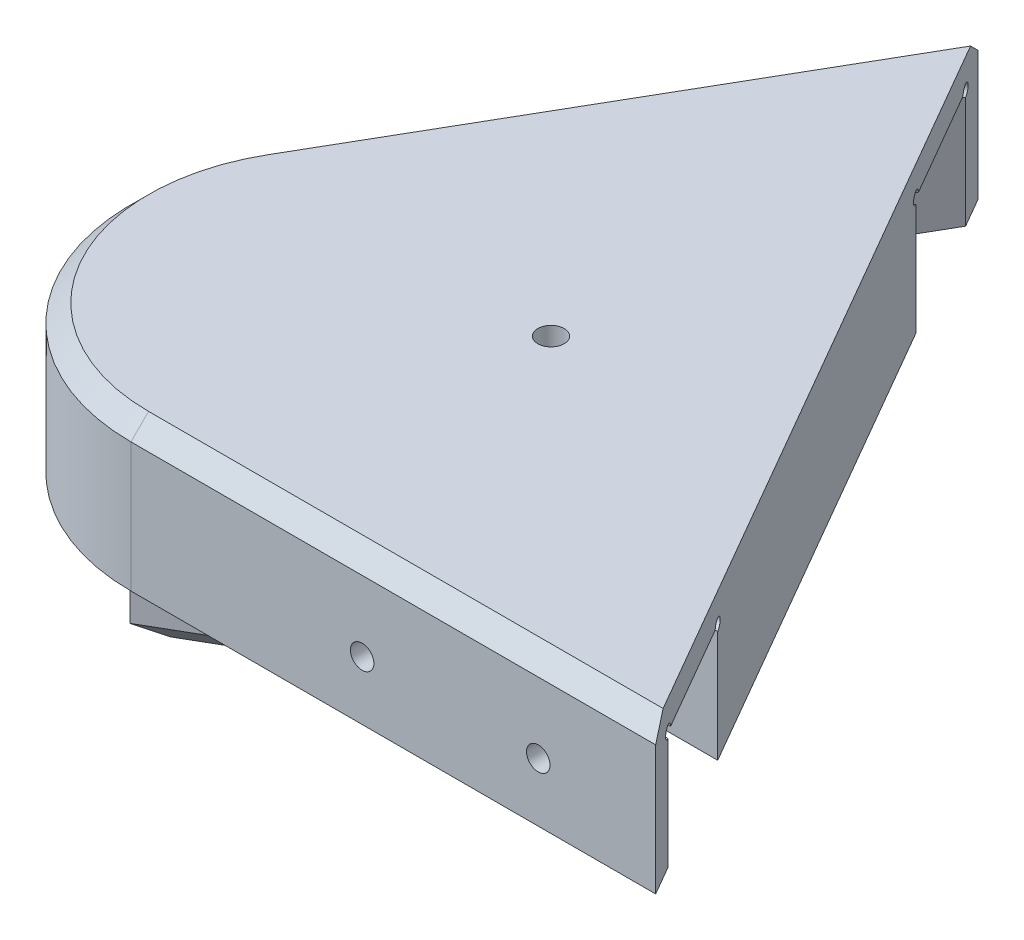
SolidWorks part; units mm, degrees
ref_plane "Front Plane" through (0, 0, 0) normal (0, 0, 1) x (1, 0, 0)
ref_plane "Top Plane" through (0, 0, 0) normal (0, 1, 0) x (1, 0, 0)
ref_plane "Right Plane" through (0, 0, 0) normal (1, 0, 0) x (0, 0, -1)
sketch "Sketch1" plane through (0, 0, 0) normal (0, 1, 0) x (1, 0, 0)
  line L0 (0, 0) -> (150, 0)
  line L1 (0, 0) -> (75, 129.9038)
  line L2 (75, 129.9038) -> (150, 0)
  dimension "D1" = 60
  dimension "D2" = 150
  dimension "D3" = 60
extrude "Boss-Extrude1" add sketch "Sketch1" along normal blind 25
sketch "Sketch2" plane through (0, 0, 0) normal (0, 1, 0) x (1, 0, 0)
  line L0 (0, 0) -> (150, 0) construction
  line L1 (74, 5) -> (228.3519, 5)
  line L2 (74, 5) -> (74, 25)
  line L3 (74, 25) -> (228.3519, 25)
  line L4 (228.3519, 5) -> (228.3519, 25)
  line L5 (41.3301, 61.5859) -> (92.5147, 150.2401)
  line L6 (92.5147, 150.2401) -> (109.8352, 140.2401)
  line L7 (109.8352, 140.2401) -> (58.6506, 51.5859)
  line L8 (58.6506, 51.5859) -> (41.3301, 61.5859)
  line L9 (75, 129.9038) -> (0, 0) construction
  dimension "D1" = 20
  dimension "D2" = 5
  dimension "D3" = 74
  dimension "D4" = 20
  dimension "D5" = 74
  dimension "D6" = 5
extrude "Cut-Extrude2" cut sketch "Sketch2" along normal blind 20
sketch "Sketch4" plane through (0, 0, 0) normal (0, 1, 0) x (1, 0, 0)
  line L5 (135.5662, 25) -> (89.4338, 104.9038) construction
  line L6 (0, 0) -> (52.9457, 91.7047) construction
  line L7 (68.4424, 27.9682) -> (51.1219, 17.9682)
  line L8 (68.4424, 27.9682) -> (58.4424, 45.2887)
  line L9 (58.4424, 45.2887) -> (41.1219, 35.2887)
  line L10 (51.1219, 17.9682) -> (41.1219, 35.2887)
  line L11 (68.4424, 27.9682) -> (41.1219, 35.2887) construction
  line L12 (58.4424, 45.2887) -> (51.1219, 17.9682) construction
  line L14 (75, 129.9038) -> (0, 0) construction
  line L15 (0, 0) -> (130.8784, 0) construction
  line L16 (0, 0) -> (150, 0) construction
  point P0 (54.7821, 31.6285)
  dimension "D1" = 20
  dimension "D2" = 20
  dimension "D3" = 53.2569
extrude "Cut-Extrude3" cut sketch "Sketch4" along normal blind 20
sketch "Sketch5" plane through (0, 0, 0) normal (0, -1, 0) x (1, 0, 0)
  line L0 (69.0177, -51.9717) -> (69.7497, -54.7038) construction
  line L1 (69.7497, -54.7038) -> (76.2449, -58.4538) construction
  line L2 (76.2449, -58.4538) -> (74.7449, -61.0519) construction
  line L3 (74.7449, -61.0519) -> (77.343, -62.5519) construction
  line L4 (77.343, -62.5519) -> (78.843, -59.9538) construction
  line L5 (78.843, -59.9538) -> (85.3382, -63.7038) construction
  line L6 (85.3382, -63.7038) -> (88.0703, -62.9717) construction
  line L7 (88.0703, -62.9717) -> (98.5703, -44.7852) construction
  line L8 (98.5703, -44.7852) -> (97.8382, -42.0532) construction
  line L9 (97.8382, -42.0532) -> (91.343, -38.3032) construction
  line L10 (91.343, -38.3032) -> (92.843, -35.7051) construction
  line L11 (92.843, -35.7051) -> (90.2449, -34.2051) construction
  line L12 (90.2449, -34.2051) -> (88.7449, -36.8032) construction
  line L13 (88.7449, -36.8032) -> (82.2497, -33.0532) construction
  line L14 (82.2497, -33.0532) -> (79.5177, -33.7852) construction
  line L15 (79.5177, -33.7852) -> (69.0177, -51.9717) construction
  line L16 (68.5884, -51.9152) -> (69.4063, -54.9674)
  line L17 (69.4063, -54.9674) -> (75.6985, -58.6002)
  line L18 (75.6985, -58.6002) -> (74.1985, -61.1983)
  line L19 (74.1985, -61.1983) -> (77.4894, -63.0983)
  line L20 (77.4894, -63.0983) -> (78.9894, -60.5002)
  line L21 (78.9894, -60.5002) -> (85.2817, -64.133)
  line L22 (85.2817, -64.133) -> (88.3338, -63.3152)
  line L23 (88.3338, -63.3152) -> (98.9995, -44.8417)
  line L24 (98.9995, -44.8417) -> (98.1817, -41.7896)
  line L25 (98.1817, -41.7896) -> (91.8894, -38.1567)
  line L26 (91.8894, -38.1567) -> (93.3894, -35.5587)
  line L27 (93.3894, -35.5587) -> (90.0985, -33.6587)
  line L28 (90.0985, -33.6587) -> (88.5985, -36.2567)
  line L29 (88.5985, -36.2567) -> (82.3063, -32.6239)
  line L30 (82.3063, -32.6239) -> (79.2541, -33.4417)
  line L31 (79.2541, -33.4417) -> (68.5884, -51.9152)
  dimension "D1" = 0.4
extrude "Cut-Extrude4" cut sketch "Sketch5" against normal offset from surface (20 mm away) 5 up to face at (75, 25, -43.3013)
sketch "Sketch6" plane through (0, 20, 0) normal (0, -1, 0) x (1, 0, 0)
  circle A0 centre (83.794, -48.3785) radius 2.25
  dimension "D1" = 4.5
extrude "Cut-Extrude5" cut sketch "Sketch6" against normal through all
sketch "Sketch7" plane through (0, 0, 0) normal (-0.866, 0, -0.5) x (-0.5, 0, 0.866)
  line L0 (-150, 0) -> (0, 0) construction
  line L1 (-150, 25) -> (-150, 0) construction
  circle A0 centre (-130, 10) radius 2
  circle A1 centre (-100, 10) radius 2
  point P8 (0, 0)
  dimension "D1" = 4
  dimension "D2" = 10
  dimension "D3" = 20
  dimension "D4" = 30
extrude "Cut-Extrude6" cut sketch "Sketch7" against normal blind 10
sketch "Sketch8" plane through (0, 0, 0) normal (0, 0, 1) x (1, 0, 0)
  line L0 (150, 25) -> (150, 0) construction
  line L1 (0, 0) -> (150, 0) construction
  circle A0 centre (130, 10) radius 2
  circle A1 centre (100, 10) radius 2
  point P8 (0, 0)
  dimension "D1" = 4
  dimension "D2" = 20
  dimension "D3" = 10
  dimension "D4" = 30
extrude "Cut-Extrude7" cut sketch "Sketch8" against normal blind 10
sketch "Sketch9" plane through (46.1219, 0, -26.6285) normal (0.866, 0, -0.5) x (-0.5, 0, -0.866)
  line L0 (10, 0) -> (-10, 0) construction
  line L1 (10, 20) -> (10, 0) construction
  circle A0 centre (0, 10) radius 2
  point P4 (0, 0)
  dimension "D3" = 4
  dimension "D1" = 10
  dimension "D2" = 10
extrude "Cut-Extrude8" cut sketch "Sketch9" against normal through all
ref_plane "Plane1" through (42.6578, 0, -24.6285) normal (0.866, 0, -0.5) x (-0.5, 0, -0.866)
sketch "Sketch10" plane through (42.6578, 0, -24.6285) normal (0.866, 0, -0.5) x (-0.5, 0, -0.866)
  circle A0 centre (0, 10) radius 4
  dimension "D1" = 8
extrude "Cut-Extrude9" cut sketch "Sketch10" against normal through all
sketch "Sketch20" plane through (0, 0, 0) normal (0, -1, 0) x (1, 0, 0)
  line L0 (51.1219, -17.9682) -> (41.1219, -35.2887)
  line L1 (41.1219, -35.2887) -> (58.4424, -45.2887)
  line L2 (58.4424, -45.2887) -> (68.4424, -27.9682)
  line L3 (68.4424, -27.9682) -> (51.1219, -17.9682)
  line L4 (51.1219, -17.9682) -> (68.4424, -27.9682) construction
  line L5 (41.1219, -35.2887) -> (51.1219, -17.9682) construction
  line L6 (68.4424, -27.9682) -> (58.4424, -45.2887) construction
  line L7 (58.4424, -45.2887) -> (41.1219, -35.2887) construction
  line L8 (75.2725, -26.1381) -> (49.2917, -11.1381)
  line L9 (49.2917, -11.1381) -> (34.2917, -37.1189)
  line L10 (34.2917, -37.1189) -> (60.2725, -52.1189)
  line L11 (60.2725, -52.1189) -> (75.2725, -26.1381)
  point P16 (51.1219, -17.9682)
  point P18 (58.4424, -45.2887)
  dimension "D1" = 5
extrude "Boss-Extrude5" add sketch "Sketch20" along normal blind 20
chamfer "Chamfer2" distance 5.35 angle 45 4 edges at (62.2821, 0, -18.6381) (47.2821, 0, -44.6189) (41.7917, 0, -24.1285) (67.7725, 0, -39.1285)
chamfer "Chamfer3" distance 4 angle 45 4 edges at (67.7725, -20, -39.1285) (47.2821, -20, -44.6189) (41.7917, -20, -24.1285) (62.2821, -20, -18.6381)
sketch "Sketch15" plane through (0, 20, 0) normal (0, -1, 0) x (1, 0, 0)
  line L0 (57.2707, -21.5182) -> (56.2707, -23.2503)
  line L2 (56.2707, -23.2503) -> (61.2936, -26.1503)
  line L3 (61.2936, -26.1503) -> (62.2936, -24.4182)
  line L4 (62.2936, -24.4182) -> (57.2707, -21.5182)
  line L5 (49.7821, -40.2887) -> (47.2707, -38.8387)
  line L7 (58.4424, -45.2887) -> (41.1219, -35.2887) construction
  line L8 (47.2707, -38.8387) -> (48.2707, -37.1067)
  line L9 (48.2707, -37.1067) -> (53.2936, -40.0067)
  line L10 (53.2936, -40.0067) -> (52.2936, -41.7387)
  line L11 (52.2936, -41.7387) -> (49.7821, -40.2887)
  line L12 (68.4424, -27.9682) -> (58.4424, -45.2887) construction
  line L14 (68.4424, -27.9682) -> (58.4424, -45.2887) construction
  line L15 (41.1219, -35.2887) -> (58.4424, -45.2887) construction
  line L16 (51.1219, -17.9682) -> (68.4424, -27.9682) construction
  point P2 (62.2936, -24.4182)
  point P8 (0, 0)
  point P9 (49.2454, -40.0067)
  point P19 (49.7821, -40.2887)
  dimension "D1" = 5.8
  dimension "D2" = 7.1
  dimension "D3" = 2
  dimension "D4" = 2
  dimension "D5" = 7.1
  dimension "D6" = 5.8
extrude "Boss-Extrude2" add sketch "Sketch15" along normal up to surface (40 mm away) up to face at (54.7821, -20, -31.6285)
sketch "Sketch11" plane through (0, 20, 0) normal (0, -1, 0) x (1, 0, 0)
  circle A0 centre (58.6506, -51.5859) radius 1
  circle A1 centre (41.3301, -61.5859) radius 1
  circle A2 centre (74, -25) radius 1
  circle A3 centre (74, -5) radius 1
  circle A4 centre (51.1219, -17.9682) radius 1
  circle A5 centre (68.4424, -27.9682) radius 1
  circle A6 centre (41.1219, -35.2887) radius 1
  circle A7 centre (58.4424, -45.2887) radius 1
  dimension "D1" = 2
extrude "Cut-Extrude10" cut sketch "Sketch11" along normal through all
sketch "Sketch12" plane through (37, 0, -64.0859) normal (0.5, 0, -0.866) x (-0.866, 0, -0.5)
  circle A0 centre (-25, 20) radius 1
  circle A1 centre (-5, 20) radius 1
  dimension "D1" = 2
  dimension "D2" = 2
extrude "Cut-Extrude11" cut sketch "Sketch12" along normal through all
sketch "Sketch13" plane through (74, 0, 0) normal (1, 0, 0) x (0, 0, -1)
  circle A0 centre (5, 20) radius 1
  circle A1 centre (25, 20) radius 1
  dimension "D1" = 2
  dimension "D2" = 2
extrude "Cut-Extrude12" cut sketch "Sketch13" along normal through all
fillet "Fillet2" radius 2 4 edges at (58.6506, 20, -51.5859) (41.3301, 20, -61.5859) (74, 20, -25) (74, 20, -5)
sketch "Sketch14" plane through (0, 0, 0) normal (0, -1, 0) x (1, 0, 0)
  line L0 (130.3701, -28) -> (89.4338, -98.9038)
  line L1 (89.4338, -98.9038) -> (80.3423, -83.1569)
  line L2 (80.3423, -83.1569) -> (112.1872, -28)
  line L3 (112.1872, -28) -> (130.3701, -28)
  line L4 (135.5662, -25) -> (82.1072, -25) construction
  line L5 (135.5662, -25) -> (89.4338, -104.9038) construction
  line L6 (62.7043, -58.6069) -> (89.4338, -104.9038) construction
  line L7 (59.1506, -52.4519) -> (89.4338, -104.9038) construction
  line L8 (98.9995, -44.8417) -> (88.3338, -63.3152) construction
  dimension "D1" = 3
  dimension "D2" = 3
  dimension "D3" = 3
  dimension "D4" = 3
extrude "Cut-Extrude13" cut sketch "Sketch14" against normal offset from surface (22 mm away) 3 up to face at (83.794, 25, -50.6285)
fillet "Fillet3" radius 35 1 edges at (0, 19.5, 0)
chamfer "Chamfer1" distance 3 angle 45 3 edges at (52.6554, 25, -91.2019) (105.3109, 25, 0) (30.3109, 25, -17.5)
